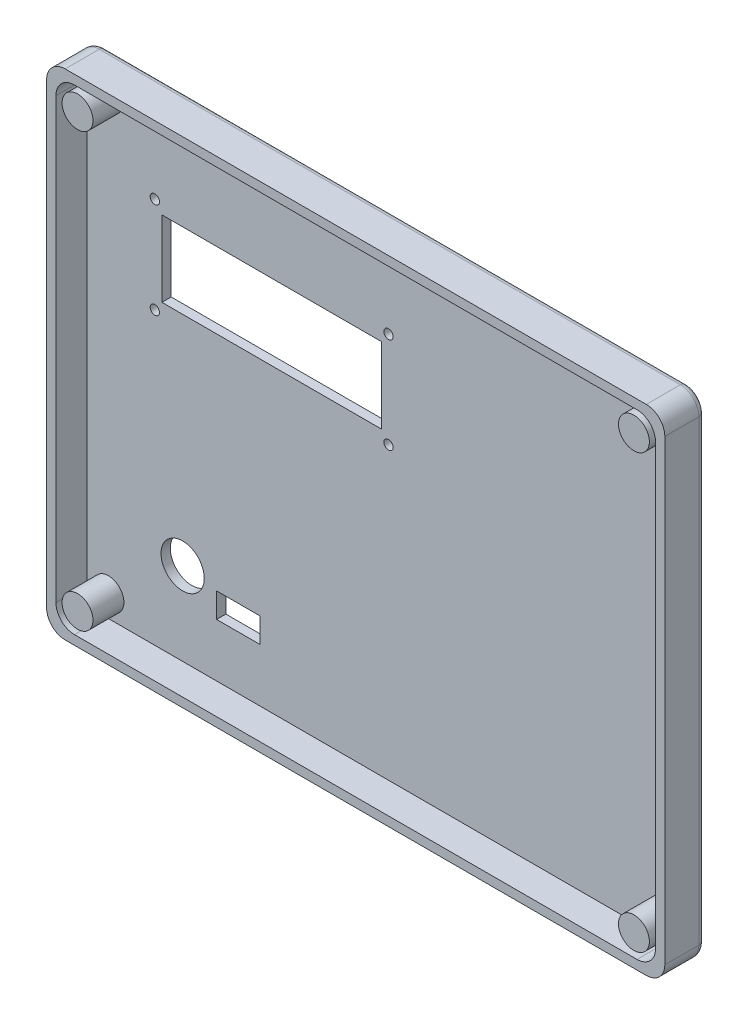
SolidWorks part; units mm, degrees
ref_plane "Plan de face" through (0, 0, 0) normal (0, 0, 1) x (1, 0, 0)
ref_plane "Plan de dessus" through (0, 0, 0) normal (0, 1, 0) x (1, 0, 0)
ref_plane "Plan de droite" through (0, 0, 0) normal (1, 0, 0) x (0, 0, -1)
sketch "Esquisse1" plane through (0, 0, 0) normal (0, 0, 1) x (1, 0, 0)
  line L1 (-91, -77) -> (91, -77)
  line L2 (-97, -71) -> (-97, 71)
  line L3 (-91, 77) -> (91, 77)
  line L4 (97, -71) -> (97, 71)
  line L5 (-97, -77) -> (97, 77) construction
  line L6 (-97, 77) -> (97, -77) construction
  line L7 (-94, -80) -> (94, -80)
  line L8 (-100, -74) -> (-100, 74)
  line L9 (-94, 80) -> (94, 80)
  line L10 (100, -74) -> (100, 74)
  line L11 (-100, -80) -> (100, 80) construction
  line L12 (-100, 80) -> (100, -80) construction
  arc A0 (91, 77) -> (97, 71) centre (91, 71) cw
  arc A1 (-91, -77) -> (-97, -71) centre (-91, -71) cw
  arc A2 (91, -77) -> (97, -71) centre (91, -71) ccw
  arc A3 (-97, 71) -> (-91, 77) centre (-91, 71) cw
  arc A4 (94, 80) -> (100, 74) centre (94, 74) cw
  arc A5 (94, -80) -> (100, -74) centre (94, -74) ccw
  arc A6 (-94, -80) -> (-100, -74) centre (-94, -74) cw
  arc A7 (-100, 74) -> (-94, 80) centre (-94, 74) cw
  point P0 (0, 0)
  point P6 (0, 0)
  dimension "D5" = 6
  dimension "D1" = 154
  dimension "D2" = 194
  dimension "D3" = 3
  dimension "D4" = 3
extrude "Boss.-Extru.1" add sketch "Esquisse1" against normal blind 3 contours A3 L2 A1 L1 A2 L4 A0 L3 | A7 L8 A6 L7 A5 L10 A4 L9 L2 A3 L3 A0 L4 A2 L1 A1 region at (0, 0, 0) region at (-96.4316, -76.4316, 0)
extrude "Boss.-Extru.2" add sketch "Esquisse1<3>" along normal blind 10
sketch "Esquisse1<3>" plane through (0, 0, 0) normal (0, 0, 1) x (1, 0, 0) same geometry as "Esquisse1"
sketch "Esquisse2" plane through (0, 0, 0) normal (0, 0, 1) x (1, 0, 0)
  line L0 (-97, 71) -> (-97, -71) construction
  line L1 (-90, -70) -> (90, -70) construction
  line L2 (-90, -70) -> (-90, 70) construction
  line L3 (-90, 70) -> (90, 70) construction
  line L4 (90, -70) -> (90, 70) construction
  line L5 (-90, -70) -> (90, 70) construction
  line L6 (-90, 70) -> (90, -70) construction
  line L7 (91, 77) -> (-91, 77) construction
  circle A0 centre (-90, 70) radius 5
  circle A1 centre (90, 70) radius 5
  circle A2 centre (90, -70) radius 5
  circle A3 centre (-90, -70) radius 5
  point P0 (0, 0)
  dimension "D3" = 10
  dimension "D4" = 10
  dimension "D5" = 10
  dimension "D6" = 10
  dimension "D1" = 7
  dimension "D2" = 7
extrude "Boss.-Extru.3" add sketch "Esquisse2" along normal blind 10
fillet "Congé1" radius 2 8 edges at (-100, 0, -3) (-98.2426, -78.2426, -3) (0, -80, -3) (98.2426, -78.2426, -3) (100, 0, -3) (98.2426, 78.2426, -3) (0, 80, -3) (-98.2426, 78.2426, -3)
extrude "Boss.-Extru.4" add sketch "Esquisse2<2>" against normal blind 3.5
sketch "Esquisse2<2>" plane through (0, 0, 0) normal (0, 0, 1) x (1, 0, 0) same geometry as "Esquisse2"
sketch "Esquisse3" plane through (0, 0, -3) normal (0, 0, -1) x (-1, 0, 0)
  line L0 (100, 74) -> (100, -74) construction
  line L1 (-0.6, 17) -> (75, 17) construction
  line L2 (-0.6, 17) -> (-0.6, 48) construction
  line L3 (-0.6, 48) -> (75, 48) construction
  line L4 (75, 17) -> (75, 48) construction
  line L5 (-0.6, 17) -> (75, 48) construction
  line L6 (-0.6, 48) -> (75, 17) construction
  line L7 (94, 78) -> (-94, 78) construction
  line L9 (1.7, 20.25) -> (72.7, 20.25)
  line L10 (1.7, 20.25) -> (1.7, 44.75)
  line L11 (1.7, 44.75) -> (72.7, 44.75)
  line L12 (72.7, 20.25) -> (72.7, 44.75)
  line L13 (1.7, 20.25) -> (72.7, 44.75) construction
  line L14 (1.7, 44.75) -> (72.7, 20.25) construction
  circle A0 centre (-0.6, 48) radius 1.5
  circle A1 centre (-0.6, 17) radius 1.5
  circle A2 centre (75, 17) radius 1.5
  circle A3 centre (75, 48) radius 1.5
  point P0 (37.2, 32.5)
  point P13 (37.2, 32.5)
  dimension "D3" = 3
  dimension "D4" = 3
  dimension "D5" = 3
  dimension "D6" = 3
  dimension "D1" = 75.6
  dimension "D2" = 31
  dimension "D7" = 25
  dimension "D8" = 30
  dimension "D9" = 24.5
  dimension "D10" = 71
extrude "Enlèv. mat.-Extru.1" cut sketch "Esquisse3" against normal blind 3.5
sketch "Esquisse4" plane through (0, 0, -3) normal (0, 0, -1) x (-1, 0, 0)
  line L0 (94, -80) -> (-94, -80) construction
  line L1 (100, 74) -> (100, -74) construction
  line L3 (41, -51.75) -> (55, -51.75)
  line L4 (41, -51.75) -> (41, -59.75)
  line L5 (41, -59.75) -> (55, -59.75)
  line L6 (55, -51.75) -> (55, -59.75)
  line L7 (41, -51.75) -> (55, -59.75) construction
  line L8 (41, -59.75) -> (55, -51.75) construction
  circle A0 centre (66, -50.25) radius 7
  point P6 (48, -55.75)
  dimension "D2" = 14
  dimension "D1" = 29.75
  dimension "D3" = 34
  dimension "D4" = 14
  dimension "D5" = 8
  dimension "D6" = 11
  dimension "D7" = 1.5
extrude "Enlèv. mat.-Extru.2" cut sketch "Esquisse4" against normal blind 10
